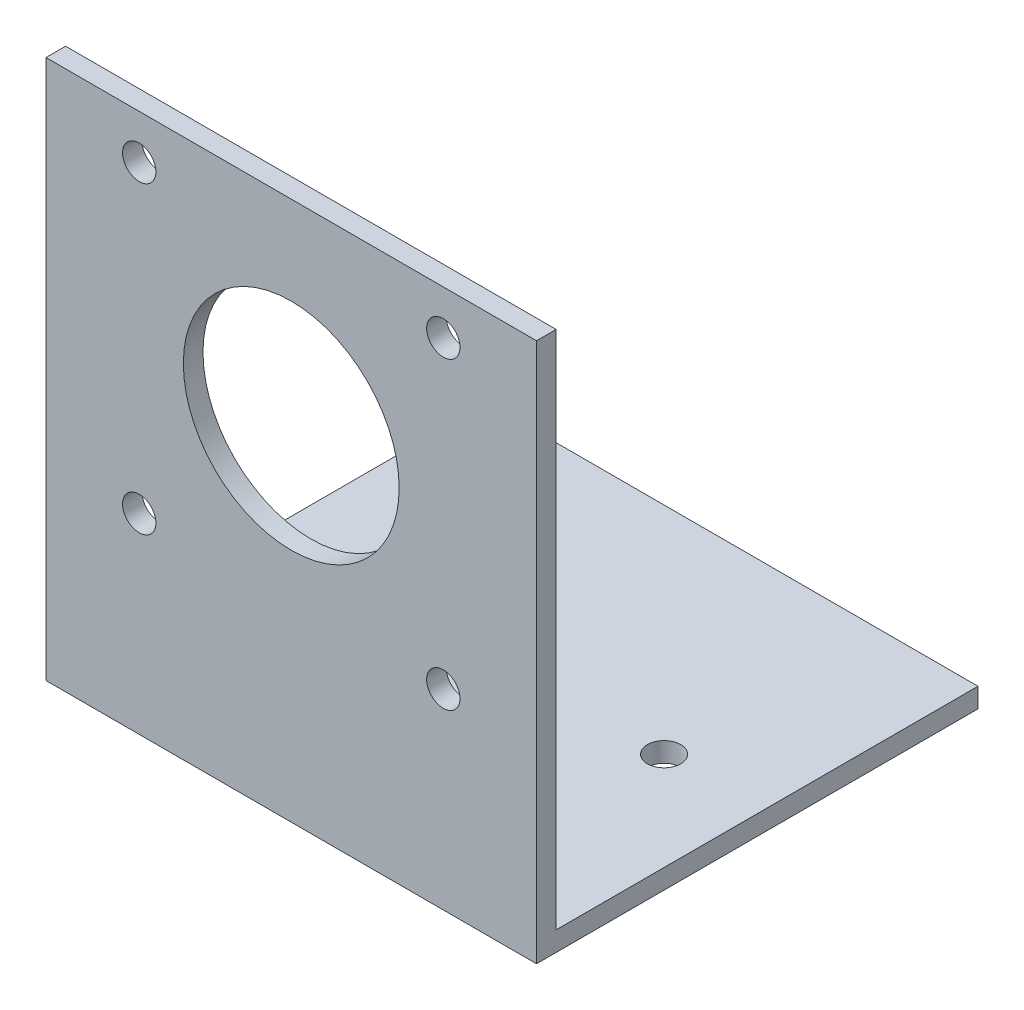
SolidWorks part; units mm, degrees
ref_plane "Front Plane" through (0, 0, 0) normal (0, 0, 1) x (1, 0, 0)
ref_plane "Top Plane" through (0, 0, 0) normal (0, 1, 0) x (1, 0, 0)
ref_plane "Right Plane" through (0, 0, 0) normal (1, 0, 0) x (0, 0, -1)
sketch "Sketch1" plane through (0, 0, 0) normal (0, 0, 1) x (1, 0, 0)
  line L1 (-25, 0) -> (25, 0)
  line L2 (-25, 0) -> (-25, 55)
  line L3 (-25, 55) -> (25, 55)
  line L4 (25, 0) -> (25, 55)
  dimension "D1" = 25
  dimension "D2" = 25
  dimension "D3" = 55
extrude "Boss-Extrude1" add sketch "Sketch1" against normal blind 2
sketch "Sketch2" plane through (0, 0, 0) normal (0, 0, 1) x (1, 0, 0)
  line L1 (-25, 0) -> (25, 0)
  line L2 (-25, 0) -> (-25, 2)
  line L3 (-25, 2) -> (25, 2)
  line L4 (25, 0) -> (25, 2)
  dimension "D1" = 25
  dimension "D2" = 25
  dimension "D3" = 2
extrude "Boss-Extrude2" add sketch "Sketch2" against normal blind 45
sketch "Sketch3" plane through (0, 0, 0) normal (0, 0, 1) x (1, 0, 0)
  circle A0 centre (-15.5, 19.5) radius 1.7
  circle A1 centre (-15.5, 50.5) radius 1.7
  circle A2 centre (15.5, 19.5) radius 1.7
  circle A3 centre (15.5, 50.5) radius 1.7
  dimension "D1" = 3.4
  dimension "D2" = 15.5
  dimension "D3" = 15.5
  dimension "D4" = 19.5
  dimension "D5" = 50.5
extrude "Cut-Extrude1" cut sketch "Sketch3" along normal through all and the other way through all
sketch "Sketch4" plane through (0, 0, 0) normal (0, 0, 1) x (1, 0, 0)
  circle A0 centre (0, 35) radius 11
  dimension "D1" = 22
  dimension "D2" = 35
extrude "Lo_tam_D22" cut sketch "Sketch4" along normal through all and the other way through all
sketch "Sketch5" plane through (0, 0, 0) normal (0, 1, 0) x (1, 0, 0)
  circle A0 centre (-15, 23) radius 1.7
  circle A1 centre (15, 23) radius 1.7
  dimension "D1" = 3.4
  dimension "D2" = 15
  dimension "D3" = 15
  dimension "D4" = 23
extrude "Hai_lo_chan_M3" cut sketch "Sketch5" along normal through all and the other way through all
